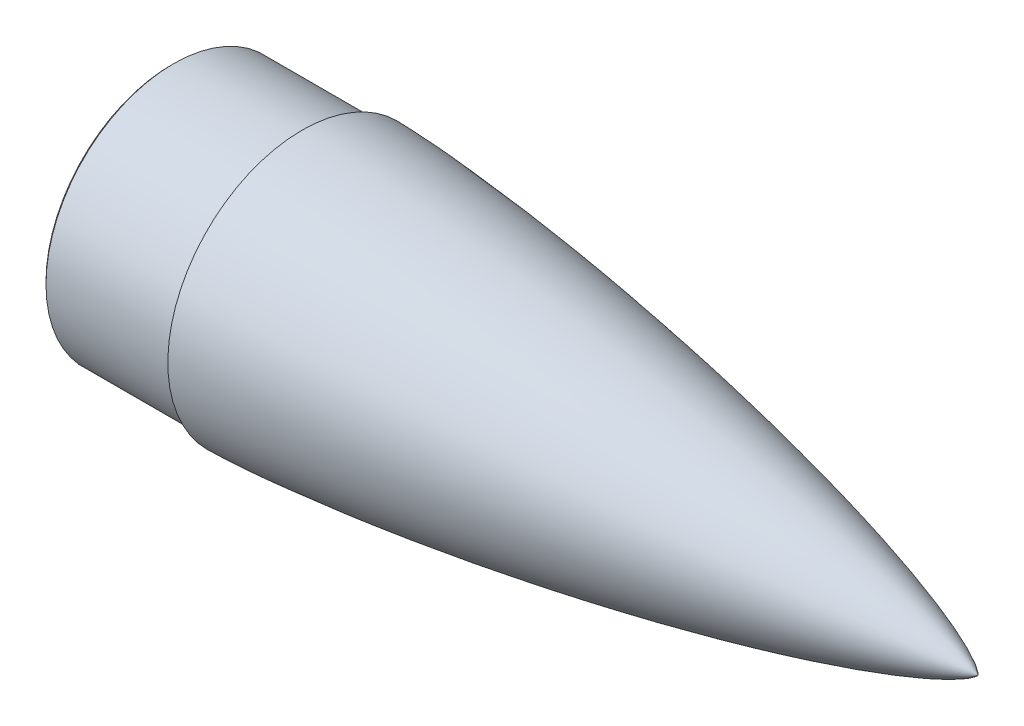
SolidWorks part; units mm, degrees
material "ABS"
ref_plane "Front Plane" through (0, 0, 0) normal (0, 0, 1) x (1, 0, 0)
ref_plane "Top Plane" through (0, 0, 0) normal (0, 1, 0) x (1, 0, 0)
ref_plane "Right Plane" through (0, 0, 0) normal (1, 0, 0) x (0, 0, -1)
ref_axis "Axis1" through (446.939, 0, 0) along (-1, 0, 0)
sketch "Sketch10" plane through (0, 0, 0) normal (0, 0, 1) x (1, 0, 0)
  line L1 (0.1246, 0) -> (486.9547, 0) construction
  line L3 (10.6078, 74.375) -> (-78.9797, 74.375)
  line L4 (410.1246, 0) -> (370.1246, 0)
  line L5 (-78.9797, 74.375) -> (-78.9797, 77.375)
  line L6 (-78.9797, 77.375) -> (0.3953, 77.375)
  line L7 (0.3953, 77.375) -> (0.3953, 81.375)
  line L8 (446.939, 0) -> (-88.2629, 0) construction
  spline S0 degree 4 poles (410.1246, 0) (410.1221, 0.0135) (410.1149, 0.0398) (410.0927, 0.0901) (410.0472, 0.173) (409.9799, 0.2736) (409.8734, 0.4124) (409.7102, 0.5994) (409.4511, 0.8632) (409.0096, 1.2601) (408.2526, 1.8596) (406.9226, 2.7821) (404.5614, 4.2111) (400.3938, 6.3987) (393.5059, 9.5313) (381.621, 14.2375) (364.5141, 20.0866) (343.0012, 26.5563) (318.1202, 33.236) (292.4827, 39.4913) (266.7321, 45.2621) (240.8911, 50.6118) (214.9738, 55.578) (188.99, 60.1833) (166.202, 63.9061) (146.6351, 66.8779) (130.3075, 69.2049) (117.2326, 70.9745) (104.1452, 72.6491) (92.683, 74.0276) (82.8506, 75.1437) (74.6519, 76.0277) (68.0898, 76.7061) (61.5248, 77.3545) (54.9566, 77.9713) (48.3855, 78.5546) (41.8112, 79.1021) (36.056, 79.5474) (31.1211, 79.9027) (27.0073, 80.1796) (23.7154, 80.3889) (20.0983, 80.6044) (16.7295, 80.7887) (13.6093, 80.9437) (10.7378, 81.0719) (8.4403, 81.1644) (6.1423, 81.2463) (4.1312, 81.3058) (2.4071, 81.3474) (1.2576, 81.366) (0.6827, 81.374) (0.3953, 81.375) knots 0 0 0 0 0 0.00013 0.00026 0.00052 0.0009 0.00128 0.001925 0.002882 0.004418 0.006927 0.011111 0.018279 0.030673 0.051704 0.083102 0.139909 0.202703 0.265496 0.32829 0.391083 0.453877 0.516671 0.579464 0.642258 0.673655 0.705051 0.736448 0.767845 0.799242 0.81494 0.830639 0.846337 0.862036 0.877734 0.893432 0.909131 0.924829 0.932678 0.940527 0.948377 0.956226 0.967169 0.972641 0.978113 0.983585 0.989056 0.994528 0.997264 1 1 1 1 1 construction
  spline S1 degree 4 poles (410.1246, 0) (410.1221, 0.0135) (410.1149, 0.0398) (410.0927, 0.0901) (410.0472, 0.173) (409.9799, 0.2736) (409.8734, 0.4124) (409.7102, 0.5994) (409.4511, 0.8632) (409.0096, 1.2601) (408.2526, 1.8596) (406.9226, 2.7821) (404.5614, 4.2111) (400.3938, 6.3987) (393.5059, 9.5313) (381.621, 14.2375) (364.5141, 20.0866) (343.0012, 26.5563) (318.1202, 33.236) (292.4827, 39.4913) (266.7321, 45.2621) (240.8911, 50.6118) (214.9738, 55.578) (188.99, 60.1833) (166.202, 63.9061) (146.6351, 66.8779) (130.3075, 69.2049) (117.2326, 70.9745) (104.1452, 72.6491) (92.683, 74.0276) (82.8506, 75.1437) (74.6519, 76.0277) (68.0898, 76.7061) (61.5248, 77.3545) (54.9566, 77.9713) (48.3855, 78.5546) (41.8112, 79.1021) (36.056, 79.5474) (31.1211, 79.9027) (27.0073, 80.1796) (23.7154, 80.3889) (20.0983, 80.6044) (16.7295, 80.7887) (13.6093, 80.9437) (10.7378, 81.0719) (8.4403, 81.1644) (6.1423, 81.2463) (4.1312, 81.3058) (2.4071, 81.3474) (1.2576, 81.366) (0.6827, 81.374) (0.3953, 81.375) knots 0 0 0 0 0 0.00013 0.00026 0.00052 0.0009 0.00128 0.001925 0.002882 0.004418 0.006927 0.011111 0.018279 0.030673 0.051704 0.083102 0.139909 0.202703 0.265496 0.32829 0.391083 0.453877 0.516671 0.579464 0.642258 0.673655 0.705051 0.736448 0.767845 0.799242 0.81494 0.830639 0.846337 0.862036 0.877734 0.893432 0.909131 0.924829 0.932678 0.940527 0.948377 0.956226 0.967169 0.972641 0.978113 0.983585 0.989056 0.994528 0.997264 1 1 1 1 1
  spline S2 degree 4 poles (370.1246, 0) (370.1224, 0.0123) (370.116, 0.0363) (370.0963, 0.0824) (370.0563, 0.1573) (369.9976, 0.2476) (369.9051, 0.372) (369.7625, 0.5408) (369.5335, 0.7812) (369.1415, 1.1443) (368.4657, 1.695) (367.2788, 2.5416) (365.1671, 3.8555) (361.4569, 5.8578) (355.3712, 8.7067) (344.9189, 12.9749) (329.9118, 18.2779) (311.0559, 24.1485) (289.238, 30.2213) (266.7491, 35.917) (244.155, 41.1787) (221.4767, 46.0629) (198.727, 50.6028) (175.9152, 54.8187) (155.9058, 58.2316) (138.7227, 60.9598) (124.3828, 63.0986) (112.8989, 64.7269) (101.4032, 66.2696) (91.3342, 67.5412) (82.6964, 68.572) (75.4934, 69.3895) (69.7281, 70.0175) (63.96, 70.6184) (58.1889, 71.1907) (52.4149, 71.7327) (46.6379, 72.2424) (41.5805, 72.6578) (37.2437, 72.9898) (33.6283, 73.2492) (30.7353, 73.4456) (27.5794, 73.6468) (24.1602, 73.8474) (20.9707, 74.0149) (18.011, 74.1502) (15.544, 74.2471) (13.8166, 74.3045) (12.3358, 74.3455) (11.3484, 74.3648) (10.8547, 74.3734) (10.6078, 74.375) knots 0 0 0 0 0 0.000135 0.00027 0.00054 0.00092 0.001299 0.001947 0.002931 0.004512 0.007081 0.01138 0.018708 0.031424 0.052705 0.084103 0.14091 0.203703 0.266497 0.329291 0.392084 0.454878 0.517672 0.580465 0.643259 0.674656 0.706052 0.737449 0.768846 0.800243 0.815941 0.831639 0.847338 0.863036 0.878735 0.894433 0.910132 0.92583 0.933679 0.941528 0.949378 0.957227 0.96792 0.978613 0.98396 0.989307 0.994653 0.997327 1 1 1 1 1 construction
  spline S3 degree 4 poles (370.1246, 0) (370.1224, 0.0123) (370.116, 0.0363) (370.0963, 0.0824) (370.0563, 0.1573) (369.9976, 0.2476) (369.9051, 0.372) (369.7625, 0.5408) (369.5335, 0.7812) (369.1415, 1.1443) (368.4657, 1.695) (367.2788, 2.5416) (365.1671, 3.8555) (361.4569, 5.8578) (355.3712, 8.7067) (344.9189, 12.9749) (329.9118, 18.2779) (311.0559, 24.1485) (289.238, 30.2213) (266.7491, 35.917) (244.155, 41.1787) (221.4767, 46.0629) (198.727, 50.6028) (175.9152, 54.8187) (155.9058, 58.2316) (138.7227, 60.9598) (124.3828, 63.0986) (112.8989, 64.7269) (101.4032, 66.2696) (91.3342, 67.5412) (82.6964, 68.572) (75.4934, 69.3895) (69.7281, 70.0175) (63.96, 70.6184) (58.1889, 71.1907) (52.4149, 71.7327) (46.6379, 72.2424) (41.5805, 72.6578) (37.2437, 72.9898) (33.6283, 73.2492) (30.7353, 73.4456) (27.5794, 73.6468) (24.1602, 73.8474) (20.9707, 74.0149) (18.011, 74.1502) (15.544, 74.2471) (13.8166, 74.3045) (12.3358, 74.3455) (11.3484, 74.3648) (10.8547, 74.3734) (10.6078, 74.375) knots 0 0 0 0 0 0.000135 0.00027 0.00054 0.00092 0.001299 0.001947 0.002931 0.004512 0.007081 0.01138 0.018708 0.031424 0.052705 0.084103 0.14091 0.203703 0.266497 0.329291 0.392084 0.454878 0.517672 0.580465 0.643259 0.674656 0.706052 0.737449 0.768846 0.800243 0.815941 0.831639 0.847338 0.863036 0.878735 0.894433 0.910132 0.92583 0.933679 0.941528 0.949378 0.957227 0.96792 0.978613 0.98396 0.989307 0.994653 0.997327 1 1 1 1 1
  dimension "D4" = 77.375
  dimension "D1" = 81.375
  dimension "D3" = 410
  dimension "D5" = 370
  dimension "D6" = 79.375
  dimension "D2" = 3
revolve "Revolve1" add sketch "Sketch10" angle 360 about axis through (446.939, 0, 0) along (-1, 0, 0)
chamfer "Chamfer1" distance 1.5 angle 45 1 edges at (-78.9797, 0, -77.375)
equation "\"TubeDiameter\" = 6.250in"
equation "\"D1@Sketch10\"=(\"TubeDiameter\"/2)+2mm"
equation "\"D6@Sketch10\"=\"TubeDiameter\"/2"
equation "\"D4@Sketch10\"=\"TubeDiameter\"/2-2mm"
